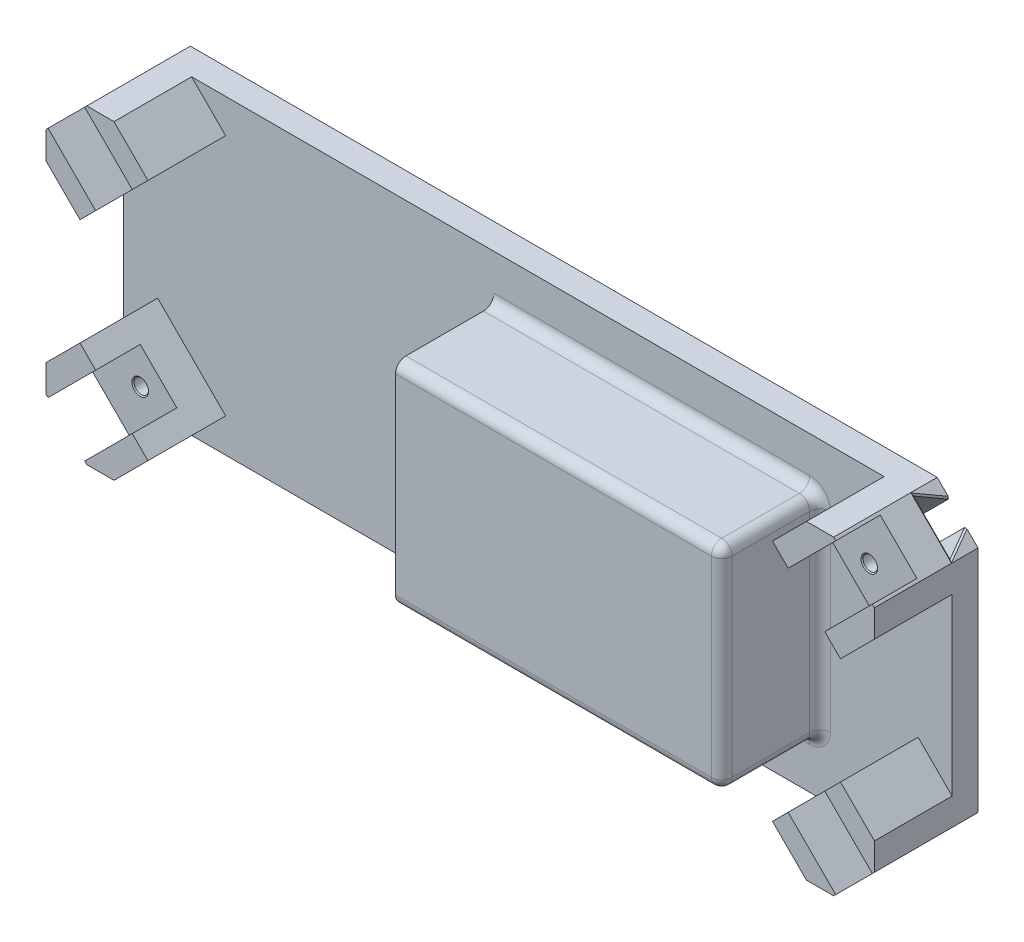
SolidWorks part; units mm, degrees
ref_plane "Front Plane" through (0, 0, 0) normal (0, 0, 1) x (1, 0, 0)
ref_plane "Top Plane" through (0, 0, 0) normal (0, 1, 0) x (1, 0, 0)
ref_plane "Right Plane" through (0, 0, 0) normal (1, 0, 0) x (0, 0, -1)
sketch "Sketch1" plane through (10.8587, 0, 0) normal (0, 0, 1) x (1, 0, 0)
  line L0 (-52.705, 21.59) -> (48.895, 21.59)
  line L1 (52.705, -25.4) -> (-52.705, -25.4)
  line L2 (52.705, -25.4) -> (52.705, 25.4)
  line L3 (52.705, 25.4) -> (-52.705, 25.4)
  line L4 (-52.705, -25.4) -> (-52.705, 25.4)
  line L5 (52.705, -25.4) -> (-52.705, 25.4) construction
  line L6 (52.705, 25.4) -> (-52.705, -25.4) construction
  line L7 (48.895, 21.59) -> (48.895, -22.86)
  line L8 (48.895, -22.86) -> (-52.705, -22.86)
  line L9 (-52.705, 13.97) -> (-6.985, 13.97)
  line L10 (-6.985, 13.97) -> (-6.985, -6.35)
  line L11 (-6.985, -6.35) -> (-52.705, -6.35)
  point P0 (0, 0)
  dimension "D1" = 105.41
  dimension "D2" = 50.8
  dimension "D3" = 101.6
  dimension "D4" = 44.45
  dimension "D5" = 3.81
  dimension "D6" = 45.72
  dimension "D7" = 20.32
  dimension "D8" = 7.62
extrude "Boss-Extrude1" add sketch "Sketch1" along normal blind 27.432 contours L7 L8 L4 L1 L2 L3 L0 region at (-40.6761, 23.495, 0)
extrude "Boss-Extrude2" add sketch "Sketch1<3>" along normal blind 5.08 contours L10 L11 L4 L8 L7 L0 L9 region at (16.19, -1.7862, 0)
sketch "Sketch1<3>" plane through (10.8587, 0, 0) normal (0, 0, 1) x (1, 0, 0) same geometry as "Sketch1"
sketch "Sketch4" plane through (10.8587, 0, 5.08) normal (0, 0, 1) x (1, 0, 0)
  line L0 (-52.705, 21.59) -> (48.895, 21.59) construction
  line L1 (-44.7859, 21.59) -> (-47.9241, 21.59)
  line L2 (-47.9241, 21.59) -> (-49.4932, 18.8722)
  line L3 (-49.4932, 18.8722) -> (-47.9241, 16.1544)
  line L4 (-47.9241, 16.1544) -> (-44.7859, 16.1544)
  line L5 (-44.7859, 16.1544) -> (-43.2168, 18.8722)
  line L6 (-43.2168, 18.8722) -> (-44.7859, 21.59)
  line L7 (-52.705, 13.97) -> (-52.705, 21.59) construction
  line L8 (-13.3987, 22.7847) -> (-13.3987, -11.3368) construction
  line L9 (21.1266, 16.1544) -> (17.9884, 16.1544)
  line L10 (17.9884, 16.1544) -> (16.4193, 18.8722)
  line L11 (16.4193, 18.8722) -> (17.9884, 21.59)
  line L12 (17.9884, 21.59) -> (21.1266, 21.59)
  line L13 (21.1266, 21.59) -> (22.6958, 18.8722)
  line L14 (22.6958, 18.8722) -> (21.1266, 16.1544)
  line L15 (0, 0) -> (10.9329, 0) construction
  line L16 (22.6958, -18.8722) -> (21.1266, -16.1544)
  line L17 (21.1266, -21.59) -> (22.6958, -18.8722)
  line L18 (17.9884, -21.59) -> (21.1266, -21.59)
  line L19 (16.4193, -18.8722) -> (17.9884, -21.59)
  line L20 (17.9884, -16.1544) -> (16.4193, -18.8722)
  line L21 (21.1266, -16.1544) -> (17.9884, -16.1544)
  line L22 (-49.4932, -18.8722) -> (-47.9241, -16.1544)
  line L23 (-47.9241, -21.59) -> (-49.4932, -18.8722)
  line L24 (-43.2168, -18.8722) -> (-44.7859, -21.59)
  line L25 (-44.7859, -16.1544) -> (-43.2168, -18.8722)
  line L26 (-47.9241, -16.1544) -> (-44.7859, -16.1544)
  line L27 (-44.7859, -21.59) -> (-47.9241, -21.59)
  circle A0 centre (-46.355, 18.8722) radius 2.7178 construction
  circle A1 centre (-46.355, 18.8722) radius 1.524
  circle A2 centre (19.5575, 18.8722) radius 1.524
  circle A3 centre (-46.355, -18.8722) radius 1.524
  circle A4 centre (19.5575, -18.8722) radius 1.524
  dimension "D4" = 3.048
  dimension "D1" = 5.4356
  dimension "D2" = 6.35
  dimension "D3" = 2.54
extrude "Cut-Extrude1" cut sketch "Sketch4" against normal blind 2.286 contours L5 L6 L14 L2 L3 L4 A1 | L14 L13 L11 L10 L9 A2 | L26 L22 L23 L12 L24 L25 A3 | L16 L21 L20 L19 L12 L17 A4 region at (-33.2145, 20.1896, 5.08) region at (30.4163, 16.2374, 5.08) region at (32.698, -20.1896, 5.08) region at (-37.778, -17.5548, 5.08)
extrude "Cut-Extrude2" cut sketch "Sketch4<4>" against normal through all contours A1 | A2 | A3 | A4 region at (-35.4963, 18.8722, 5.08) region at (30.4163, 18.8722, 5.08) region at (-35.4963, -18.8722, 5.08) region at (30.4163, -18.8722, 5.08)
sketch "Sketch4<4>" plane through (10.8587, 0, 5.08) normal (0, 0, 1) x (1, 0, 0) same geometry as "Sketch4"
sketch "Sketch7" plane through (10.8587, 0, 27.432) normal (0, 0, 1) x (1, 0, 0)
  line L0 (0, 0) -> (-46.355, 0) construction
  line L1 (-52.705, 25.4) -> (52.705, 25.4)
  line L2 (-52.705, 25.4) -> (-52.705, 6.35)
  line L3 (-52.705, -25.4) -> (52.705, -25.4)
  line L4 (52.705, 25.4) -> (52.705, -25.4)
  line L5 (-52.705, 6.35) -> (-46.355, 6.35)
  line L7 (-52.705, -6.35) -> (-46.355, -6.35)
  line L8 (-46.355, 6.35) -> (-46.355, -6.35)
  line L9 (-52.705, -6.35) -> (-52.705, -25.4)
  line L10 (-28.575, 0) -> (-1035.3573, 0) construction
  point P11 (-46.355, 0)
  dimension "D1" = 12.7
  dimension "D2" = 6.35
extrude "Boss-Extrude3" add sketch "Sketch7" along normal blind 3.81
fillet "Fillet1" radius 2.54 5 edges at (10.8587, -25.4, 31.242) (63.5637, -25.4, 15.621) (63.5637, 0, 31.242) (63.5637, 25.4, 15.621) (10.8587, 25.4, 31.242)
chamfer "Chamfer3" distance 1.27 angle 45 9 edges at (-41.8463, 21.59, 16.256) (-41.8463, -22.86, 16.256) (-41.8463, 13.97, 27.432) (-41.8463, -14.605, 27.432) (-41.8463, -6.35, 29.337) (-38.6713, -6.35, 31.242) (-35.4963, 0, 31.242) (-38.6713, 6.35, 31.242) (-41.8463, 6.35, 29.337)
chamfer "Chamfer4" distance 0.254 angle 45 4 edges at (-33.9723, -18.8722, 0) (31.9403, -18.8722, 0) (-33.9723, 18.8722, 0) (31.9403, 18.8722, 0)
sketch "Sketch8" plane through (10.8587, 0, 5.08) normal (0, 0, 1) x (1, 0, 0)
  line L0 (-52.705, -7.62) -> (-52.705, -22.86) construction
  line L1 (48.895, 21.59) -> (-52.705, 21.59)
  line L2 (48.895, 21.59) -> (48.895, -22.86)
  line L3 (48.895, -22.86) -> (-52.705, -22.86)
  line L4 (-52.705, 21.59) -> (-52.705, -22.86)
  line L5 (48.895, -22.86) -> (-51.435, -22.86) construction
extrude "Cut-Extrude3" cut sketch "Sketch8" against normal up to surface (5.08 mm away) up to face at (-33.7183, -18.8722, 0)
chamfer "Chamfer5" distance 1.27 angle 45 2 edges at (-41.8463, -22.86, 2.54) (-41.8463, 21.59, 2.54)
sketch "Sketch9" plane through (10.8587, 0, 0) normal (0, 0, -1) x (-1, 0, 0)
  line L0 (-90.7413, 28.1) -> (-80.7413, 38.1)
  line L1 (-80.7413, -38.1) -> (102.4587, -38.1)
  line L2 (-90.7413, -28.1) -> (-90.7413, 28.1)
  line L3 (-80.7413, 38.1) -> (102.4587, 38.1)
  line L4 (112.4587, -28.1) -> (112.4587, 28.1)
  line L5 (-90.7413, -38.1) -> (112.4587, 38.1) construction
  line L6 (-90.7413, 38.1) -> (112.4587, -38.1) construction
  line L7 (-90.7413, -28.1) -> (-80.7413, -38.1)
  line L8 (102.4587, 38.1) -> (112.4587, 28.1)
  line L9 (102.4587, -38.1) -> (112.4587, -28.1)
  point P0 (10.8587, 0)
  dimension "D1" = 203.2
  dimension "D2" = 76.2
extrude "Boss-Extrude4" add sketch "Sketch9" along normal blind 6.35
fillet "Fillet2" radius 1.27 5 edges at (9.5887, -25.4, 0) (62.8198, -24.6561, 0) (63.5637, 0, 0) (62.8198, 24.6561, 0) (9.5887, 25.4, 0)
sketch "Sketch11" plane through (0, 0, 0) normal (0, 0, 1) x (1, 0, 0)
  line L0 (-101.6, 28.1) -> (-91.6, 38.1)
  line L1 (-91.6, 38.1) -> (-84.9257, 38.1)
  line L4 (-101.6, -28.1) -> (-101.6, 28.1) construction
  line L5 (-101.6, 21.4257) -> (-101.6, 28.1)
  line L6 (0, 0) -> (0, 53.0626) construction
  line L7 (-1000, 0) -> (0, 0) construction
  line L25 (-76.5885, 29.7628) -> (-93.2628, 13.0885)
  line L26 (-84.9257, 38.1) -> (-76.5885, 29.7628)
  line L28 (-101.6, 21.4257) -> (-93.2628, 13.0885)
  line L54 (0, -17.1831) -> (0, 17.1831) construction
  line L55 (84.9257, 38.1) -> (76.5885, 29.7628)
  line L56 (91.6, 38.1) -> (84.9257, 38.1)
  line L57 (101.6, 28.1) -> (91.6, 38.1)
  line L58 (101.6, 21.4257) -> (101.6, 28.1)
  line L59 (101.6, 21.4257) -> (93.2628, 13.0885)
  line L60 (76.5885, 29.7628) -> (93.2628, 13.0885)
  line L61 (17.1831, 0) -> (-17.1831, 0) construction
  line L62 (91.6, -38.1) -> (84.9257, -38.1)
  line L63 (101.6, -28.1) -> (91.6, -38.1)
  line L64 (101.6, -21.4257) -> (101.6, -28.1)
  line L65 (101.6, -21.4257) -> (93.2628, -13.0885)
  line L66 (76.5885, -29.7628) -> (93.2628, -13.0885)
  line L67 (84.9257, -38.1) -> (76.5885, -29.7628)
  line L68 (-84.9257, -38.1) -> (-76.5885, -29.7628)
  line L69 (-91.6, -38.1) -> (-84.9257, -38.1)
  line L70 (-101.6, -28.1) -> (-91.6, -38.1)
  line L71 (-101.6, -21.4257) -> (-101.6, -28.1)
  line L72 (-101.6, -21.4257) -> (-93.2628, -13.0885)
  line L73 (-76.5885, -29.7628) -> (-93.2628, -13.0885)
  dimension "D1" = 16.51
  dimension "D2" = 8.3372
extrude "Boss-Extrude5" add sketch "Sketch11" along normal blind 19.05
sketch "Sketch13" plane through (-64.85, 64.85, 0) normal (-0.7071, 0.7071, 0) x (0, 0, 1)
  line L0 (-6.35, -44.9013) -> (-6.35, -42.0708)
  line L1 (-6.35, -51.9723) -> (-6.35, -37.8302) construction
  line L2 (-6.35, -42.0708) -> (-0.254, -38.5513)
  line L3 (-0.254, -38.5513) -> (-0.254, -51.2513)
  line L4 (-0.254, -51.2513) -> (-6.35, -47.7318)
  line L5 (-6.35, -47.7318) -> (-6.35, -44.9013)
  dimension "D1" = 6.096
  dimension "D2" = 120
  dimension "D3" = 120
  dimension "D4" = 12.7
extrude "Cut-Extrude4" cut sketch "Sketch13" against normal blind 15.24
mirror "Mirror2" about plane through (0, 0, 0) normal (0, 1, 0) of "Cut-Extrude4"
mirror "Mirror3" about plane through (0, 0, 0) normal (1, 0, 0) of "Cut-Extrude4", "Mirror2"
chamfer "Chamfer7" distance 0.381 angle 45 12 edges at (99.8458, -29.8542, -3.302) (93.3542, -36.3458, -3.302) (96.6, -33.1, -0.254) (93.3542, 36.3458, -3.302) (96.6, 33.1, -0.254) (99.8458, 29.8542, -3.302) (-93.3542, 36.3458, -3.302) (-96.6, 33.1, -0.254) (-99.8458, 29.8542, -3.302) (-93.3542, -36.3458, -3.302) (-99.8458, -29.8542, -3.302) (-96.6, -33.1, -0.254)
sketch "Sketch16" plane through (0, 0, -6.35) normal (0, 0, -1) x (-1, 0, 0)
  line L0 (73.7901, 19.9888) -> (83.4888, 10.2901)
  line L1 (83.4888, 10.2901) -> (80.7947, 7.5961)
  line L2 (80.7947, 7.5961) -> (71.0961, 17.2947)
  line L3 (71.0961, 17.2947) -> (73.7901, 19.9888)
  line L4 (91.6432, 38.0568) -> (101.5568, 28.1432) construction
  line L32 (-101.6, -28.1) -> (-98.9125, -30.7875)
  line L38 (-98.9125, -30.7875) -> (-98.332, -30.8291)
  line L39 (-91.6, -38.1) -> (91.6, -38.1)
  line L40 (91.6, -38.1) -> (94.2875, -35.4125)
  line L41 (94.2875, -35.4125) -> (94.3291, -34.832)
  line L42 (94.3291, -34.832) -> (83.8222, -24.3251)
  line L43 (83.8222, -24.3251) -> (87.8251, -20.3222)
  line L44 (87.8251, -20.3222) -> (98.332, -30.8291)
  line L45 (98.332, -30.8291) -> (98.9125, -30.7875)
  line L46 (98.9125, -30.7875) -> (101.6, -28.1)
  line L47 (101.6, -28.1) -> (101.6, 28.1)
  line L48 (101.6, 28.1) -> (98.9125, 30.7875)
  line L49 (98.9125, 30.7875) -> (98.332, 30.8291)
  line L50 (98.332, 30.8291) -> (87.8251, 20.3222)
  line L51 (87.8251, 20.3222) -> (83.8222, 24.3251)
  line L52 (83.8222, 24.3251) -> (94.3291, 34.832)
  line L53 (94.3291, 34.832) -> (94.2875, 35.4125)
  line L54 (94.2875, 35.4125) -> (91.6, 38.1)
  line L55 (91.6, 38.1) -> (-91.6, 38.1)
  line L56 (-91.6, 38.1) -> (-94.2875, 35.4125)
  line L57 (-98.9125, -30.7875) -> (-98.332, -30.8291)
  line L58 (-98.332, -30.8291) -> (-87.8251, -20.3222)
  line L59 (-98.332, -30.8291) -> (-87.8251, -20.3222)
  line L60 (-87.8251, -20.3222) -> (-83.8222, -24.3251)
  line L61 (-87.8251, -20.3222) -> (-83.8222, -24.3251)
  line L62 (-83.8222, -24.3251) -> (-94.3291, -34.832)
  line L63 (-101.6, 28.1) -> (-101.6, -28.1)
  line L64 (-101.6, -28.1) -> (-98.9125, -30.7875)
  line L73 (94.2875, -35.4125) -> (94.3291, -34.832)
  line L74 (94.3291, -34.832) -> (83.8222, -24.3251)
  line L75 (83.8222, -24.3251) -> (87.8251, -20.3222)
  line L76 (87.8251, -20.3222) -> (98.332, -30.8291)
  line L77 (98.332, -30.8291) -> (98.9125, -30.7875)
  line L78 (98.9125, -30.7875) -> (101.6, -28.1)
  line L80 (101.6, 28.1) -> (98.9125, 30.7875)
  line L81 (98.9125, 30.7875) -> (98.332, 30.8291)
  line L82 (98.332, 30.8291) -> (87.8251, 20.3222)
  line L83 (87.8251, 20.3222) -> (83.8222, 24.3251)
  line L84 (83.8222, 24.3251) -> (94.3291, 34.832)
  line L85 (94.3291, 34.832) -> (94.2875, 35.4125)
  line L86 (94.2875, 35.4125) -> (91.6, 38.1)
  line L88 (-91.6, 38.1) -> (-94.2875, 35.4125)
  line L96 (-83.8222, -24.3251) -> (-94.3291, -34.832)
  line L97 (-94.3291, -34.832) -> (-94.2875, -35.4125)
  line L98 (-94.3291, -34.832) -> (-94.2875, -35.4125)
  line L99 (-94.2875, -35.4125) -> (-91.6, -38.1)
  line L100 (-94.2875, -35.4125) -> (-91.6, -38.1)
  line L101 (-94.2875, 35.4125) -> (-94.3291, 34.832)
  line L102 (-94.2875, 35.4125) -> (-94.3291, 34.832)
  line L103 (-94.3291, 34.832) -> (-83.8222, 24.3251)
  line L104 (-94.3291, 34.832) -> (-83.8222, 24.3251)
  line L105 (-83.8222, 24.3251) -> (-87.8251, 20.3222)
  line L106 (-83.8222, 24.3251) -> (-87.8251, 20.3222)
  line L107 (-87.8251, 20.3222) -> (-98.332, 30.8291)
  line L108 (-87.8251, 20.3222) -> (-98.332, 30.8291)
  line L109 (-98.332, 30.8291) -> (-98.9125, 30.7875)
  line L110 (-98.332, 30.8291) -> (-98.9125, 30.7875)
  line L111 (-98.9125, 30.7875) -> (-101.6, 28.1)
  line L112 (-98.9125, 30.7875) -> (-101.6, 28.1)
  point P14 (96.6, 33.1)
  point P16 (78.6395, 15.1395)
  dimension "D2" = 3.81
  dimension "D3" = 13.716
  dimension "D4" = 25.4
  dimension "D5" = 25.4
  dimension "D1" = 0
extrude "Cut-Extrude6" cut sketch "Sketch16" against normal blind 2.54 contours L3 L2 L1 L0 region at (-77.2924, 13.7924, -6.35)
mirror "Mirror4" about plane through (0, 0, 0) normal (0, 1, 0) of "Cut-Extrude6"
mirror "Mirror5" about plane through (0, 0, 0) normal (1, 0, 0) of "Mirror4"
sketch "Sketch17" plane through (0, 0, 19.05) normal (0, 0, 1) x (1, 0, 0)
  line L0 (-96.6, 33.1) -> (-92.1099, 37.5901)
  line L1 (-91.6, 38.1) -> (-101.6, 28.1) construction
  line L3 (20.6756, 0) -> (-20.6756, 0) construction
  line L6 (-80.4355, -25.9158) -> (-89.4158, -16.9355)
  line L8 (-101.0901, 28.6099) -> (-96.6, 33.1)
  line L10 (-92.1099, -37.5901) -> (-80.4355, -25.9158)
  line L30 (-92.1099, 37.5901) -> (-80.4355, 25.9158)
  line L31 (-93.2628, 13.0885) -> (-76.5885, 29.7628) construction
  line L32 (-80.4355, 25.9158) -> (-89.4158, 16.9355)
  line L33 (-89.4158, 16.9355) -> (-101.0901, 28.6099)
  line L34 (-96.6, -33.1) -> (-92.1099, -37.5901)
  line L35 (-101.0901, -28.6099) -> (-96.6, -33.1)
  line L36 (-89.4158, -16.9355) -> (-101.0901, -28.6099)
  line L37 (0, -20.6756) -> (0, 20.6756) construction
  line L38 (92.1099, -37.5901) -> (80.4355, -25.9158)
  line L39 (96.6, -33.1) -> (92.1099, -37.5901)
  line L40 (101.0901, -28.6099) -> (96.6, -33.1)
  line L41 (89.4158, -16.9355) -> (101.0901, -28.6099)
  line L42 (80.4355, -25.9158) -> (89.4158, -16.9355)
  line L43 (80.4355, 25.9158) -> (89.4158, 16.9355)
  line L44 (92.1099, 37.5901) -> (80.4355, 25.9158)
  line L45 (96.6, 33.1) -> (92.1099, 37.5901)
  line L46 (101.0901, 28.6099) -> (96.6, 33.1)
  line L47 (89.4158, 16.9355) -> (101.0901, 28.6099)
  dimension "D1" = 12.7
extrude "Cut-Extrude7" cut sketch "Sketch17" against normal blind 10.922
sketch "Sketch18" plane through (0, 0, 8.128) normal (0, 0, 1) x (1, 0, 0)
  line L0 (-92.1099, 37.5901) -> (-101.0901, 28.6099) construction
  line L1 (-80.4355, 25.9158) -> (-92.1099, 37.5901) construction
  circle A0 centre (-89.4158, 25.9158) radius 1.778
  dimension "D1" = 3.556
  dimension "D2" = 10.16
  dimension "D3" = 6.35
extrude "Cut-Extrude8" cut sketch "Sketch18" against normal up to surface (8.382 mm away) up to face at (-91.0771, 27.5771, -0.254)
mirror "Mirror6" about plane through (0, 0, 0) normal (0, 1, 0) of "Cut-Extrude8"
mirror "Mirror7" about plane through (0, 0, 0) normal (1, 0, 0) of "Cut-Extrude8", "Mirror6"
sketch "Sketch19" plane through (0, 0, 31.242) normal (0, 0, 1) x (1, 0, 0)
  line L1 (-67.9348, -33.6729) -> (67.9348, -33.6729)
  line L2 (-67.9348, -33.6729) -> (-67.9348, 33.6729)
  line L3 (-67.9348, 33.6729) -> (67.9348, 33.6729)
  line L4 (67.9348, -33.6729) -> (67.9348, 33.6729)
  line L5 (-67.9348, -33.6729) -> (67.9348, 33.6729) construction
  line L6 (-67.9348, 33.6729) -> (67.9348, -33.6729) construction
  point P0 (0, 0)
extrude "Cut-Extrude9" cut sketch "Sketch19" against normal up to surface (31.242 mm away) up to face at (10.3553, -0.3175, 0)
sketch "Sketch20" plane through (0, 0, 0) normal (0, 0, 1) x (1, 0, 0)
  line L0 (65.405, 22.86) -> (65.405, -21.59)
  line L1 (65.405, -21.59) -> (-10.795, -21.59)
  line L2 (65.405, 22.86) -> (-10.795, 22.86)
  line L3 (-10.795, 22.86) -> (-10.795, 26.67)
  line L4 (-10.795, 26.67) -> (69.215, 26.67)
  line L5 (69.215, 26.67) -> (69.215, -25.4)
  line L6 (69.215, -25.4) -> (-10.795, -25.4)
  line L7 (-10.795, -25.4) -> (-10.795, -21.59)
  line L8 (101.6, 21.4257) -> (101.6, -21.4257) construction
  line L9 (84.9257, -38.1) -> (-84.9257, -38.1) construction
  dimension "D1" = 52.07
  dimension "D2" = 44.45
  dimension "D3" = 3.81
  dimension "D4" = 80.01
  dimension "D5" = 76.2
  dimension "D6" = 32.385
  dimension "D7" = 12.7
extrude "Boss-Extrude6" add sketch "Sketch20" along normal blind 20.32
sketch "Sketch21" plane through (0, 0, 20.32) normal (0, 0, 1) x (1, 0, 0)
  line L1 (-10.795, 26.67) -> (69.215, 26.67)
  line L2 (-10.795, 26.67) -> (-10.795, -25.4)
  line L3 (-10.795, -25.4) -> (69.215, -25.4)
  line L4 (69.215, 26.67) -> (69.215, -25.4)
extrude "Boss-Extrude7" add sketch "Sketch21" along normal blind 3.81
fillet "Fillet3" radius 2.54 8 edges at (29.21, 26.67, 0) (69.215, 0.635, 0) (29.21, 26.67, 24.13) (69.215, 26.67, 12.065) (69.215, 0.635, 24.13) (69.215, -25.4, 12.065) (29.21, -25.4, 0) (29.21, -25.4, 24.13)
chamfer "Chamfer8" distance 1.27 angle 45 3 edges at (-10.795, -21.59, 10.16) (-10.795, 22.86, 10.16) (-10.795, 0.635, 20.32)
chamfer "Chamfer9" distance 0.254 angle 45 4 edges at (87.6378, -25.9158, 8.128) (87.6378, 25.9158, 8.128) (-87.6378, -25.9158, 8.128) (-87.6378, 25.9158, 8.128)
sketch "Sketch22" plane through (0, 0, -0.254) normal (0, 0, -1) x (-1, 0, 0)
  line L0 (-91.6432, -38.0568) -> (-101.5568, -28.1432) construction
  line L1 (-85.0164, -25.9158) -> (-87.2161, -22.1058)
  line L2 (-87.2161, -22.1058) -> (-91.6155, -22.1058)
  line L3 (-91.6155, -22.1058) -> (-93.8152, -25.9158)
  line L4 (-93.8152, -25.9158) -> (-91.6155, -29.7258)
  line L5 (-91.6155, -29.7258) -> (-87.2161, -29.7258)
  line L6 (-87.2161, -29.7258) -> (-85.0164, -25.9158)
  circle A0 centre (-89.4158, -25.9158) radius 3.81 construction
  circle A1 centre (-89.4158, -25.9158) radius 1.778 construction
  dimension "D1" = 7.62
  dimension "D2" = 10.16
  dimension "D3" = 0
extrude "Cut-Extrude10" cut sketch "Sketch22" against normal blind 3.302
mirror "Mirror8" about plane through (0, 0, 0) normal (0, 1, 0) of "Cut-Extrude10"
mirror "Mirror9" about plane through (0, 0, 0) normal (1, 0, 0) of "Cut-Extrude10", "Mirror8"
sketch "Sketch23" plane through (0, 0, 0) normal (0, 0, 1) x (1, 0, 0)
  line L16 (-93.2628, -13.0885) -> (-76.5885, -29.7628)
  line L17 (-76.5885, -29.7628) -> (-84.9257, -38.1)
  line L18 (-84.9257, -38.1) -> (84.9257, -38.1)
  line L19 (84.9257, -38.1) -> (76.5885, -29.7628)
  line L20 (76.5885, -29.7628) -> (93.2628, -13.0885)
  line L21 (93.2628, -13.0885) -> (101.6, -21.4257)
  line L22 (101.6, -21.4257) -> (101.6, 21.4257)
  line L23 (101.6, 21.4257) -> (93.2628, 13.0885)
  line L24 (93.2628, 13.0885) -> (76.5885, 29.7628)
  line L25 (76.5885, 29.7628) -> (84.9257, 38.1)
  line L26 (84.9257, 38.1) -> (-84.9257, 38.1)
  line L27 (-84.9257, 38.1) -> (-76.5885, 29.7628)
  line L28 (-76.5885, 29.7628) -> (-93.2628, 13.0885)
  line L29 (-93.2628, 13.0885) -> (-101.6, 21.4257)
  line L30 (-101.6, 21.4257) -> (-101.6, -21.4257)
  line L31 (-101.6, -21.4257) -> (-93.2628, -13.0885)
  line L32 (-93.2628, -13.0885) -> (-76.5885, -29.7628)
  line L33 (-76.5885, -29.7628) -> (-84.9257, -38.1)
  line L34 (-84.9257, -38.1) -> (84.9257, -38.1)
  line L35 (84.9257, -38.1) -> (76.5885, -29.7628)
  line L36 (76.5885, -29.7628) -> (93.2628, -13.0885)
  line L37 (93.2628, -13.0885) -> (101.6, -21.4257)
  line L38 (101.6, -21.4257) -> (101.6, 21.4257)
  line L39 (101.6, 21.4257) -> (93.2628, 13.0885)
  line L40 (93.2628, 13.0885) -> (76.5885, 29.7628)
  line L41 (76.5885, 29.7628) -> (84.9257, 38.1)
  line L42 (84.9257, 38.1) -> (-84.9257, 38.1)
  line L43 (-84.9257, 38.1) -> (-76.5885, 29.7628)
  line L44 (-76.5885, 29.7628) -> (-93.2628, 13.0885)
  line L45 (-93.2628, 13.0885) -> (-101.6, 21.4257)
  line L46 (-101.6, 21.4257) -> (-101.6, -21.4257)
  line L47 (-101.6, -21.4257) -> (-93.2628, -13.0885)
  dimension "D1" = 0
sketch "Sketch25" plane through (0, 0, 24.13) normal (0, 0, 1) x (1, 0, 0)
  line L0 (-10.795, 24.13) -> (-10.795, -22.86) construction
  line L1 (-59.5491, -50.2752) -> (111.201, -50.2752)
  line L2 (-132.791, 0.635) -> (-132.791, 51.5452)
  line L3 (-132.791, 51.5452) -> (111.201, 51.5452)
  line L4 (111.201, -50.2752) -> (111.201, 51.5452)
  line L5 (-59.5491, -19.7106) -> (111.201, 51.5452) construction
  line L6 (-132.791, 51.5452) -> (111.201, -50.2752) construction
  line L7 (-132.791, 0.635) -> (-59.5491, 0.635)
  line L8 (-59.5491, 0.635) -> (-59.5491, -50.2752)
  point P0 (-10.795, 0.635)
extrude "Cut-Extrude11" [suppressed] cut sketch "Sketch25" against normal through all
